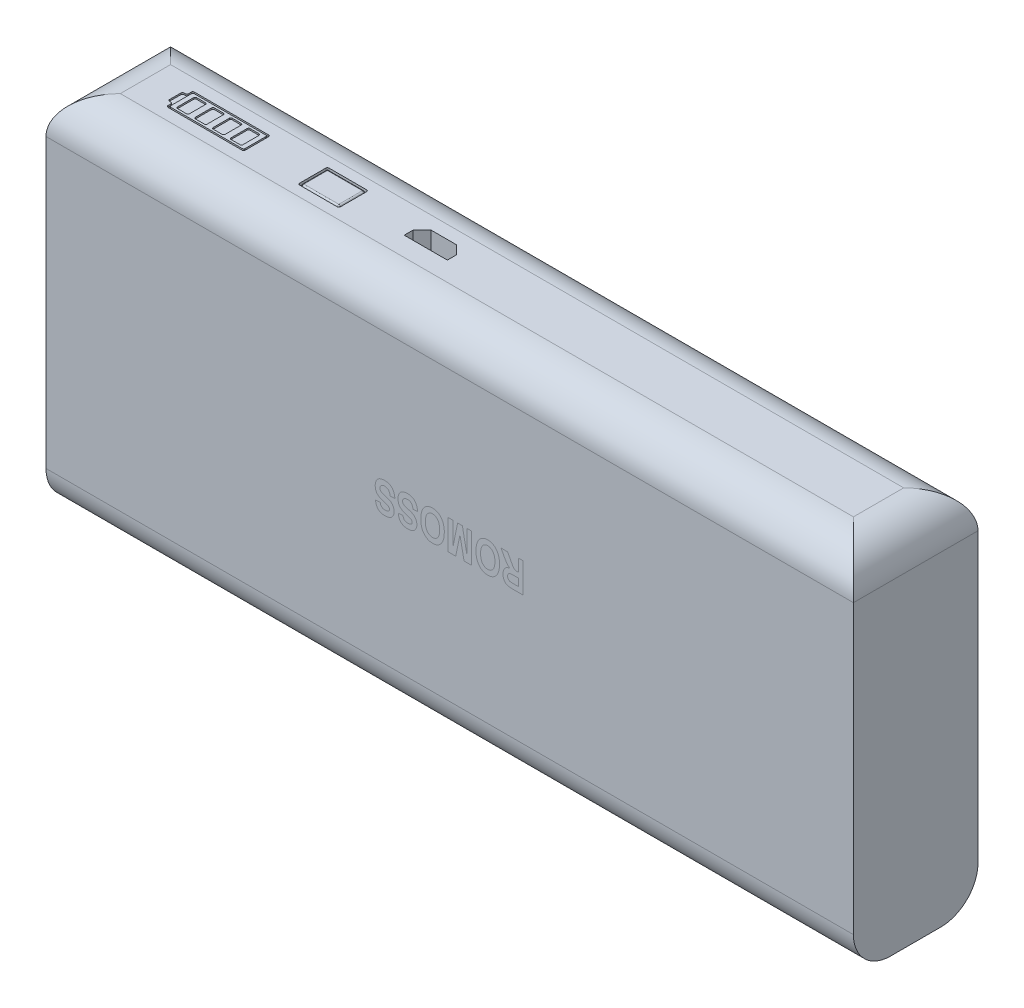
SolidWorks part; units mm, degrees
ref_plane "Front Plane" through (0, 0, 0) normal (0, 0, 1) x (1, 0, 0)
ref_plane "Top Plane" through (0, 0, 0) normal (0, 1, 0) x (1, 0, 0)
ref_plane "Right Plane" through (0, 0, 0) normal (1, 0, 0) x (0, 0, -1)
sketch "Sketch1" plane through (0, 0, 0) normal (0, 1, 0) x (1, 0, 0)
  line L1 (-68.9864, 10.6426) -> (68.9864, 10.6426)
  line L2 (-68.9864, 10.6426) -> (-68.9864, -10.6426)
  line L3 (-68.9864, -10.6426) -> (68.9864, -10.6426)
  line L4 (68.9864, 10.6426) -> (68.9864, -10.6426)
  line L5 (-68.9864, 10.6426) -> (68.9864, -10.6426) construction
  line L6 (-68.9864, -10.6426) -> (68.9864, 10.6426) construction
  point P0 (0, 0)
  dimension "D1" = 137.9728
  dimension "D2" = 21.2852
extrude "Boss-Extrude1" add sketch "Sketch1" along normal blind 61.8236
fillet "Fillet10" radius 6.35 4 edges at (-68.9864, 61.8236, 0) (0, 61.8236, 10.6426) (0, 61.8236, -10.6426) (68.9864, 61.8236, 0)
fillet "Fillet11" radius 6.35 2 edges at (0, 0, 10.6426) (0, 0, -10.6426)
sketch "Sketch3" plane through (0, 0, 10.6426) normal (0, 0, 1) x (1, 0, 0)
  line L0 (-68.9864, 33.4518) -> (68.9864, 33.4518) construction
  line L4 (-62.6364, 61.8236) -> (62.6364, 61.8236) construction
  line L5 (-68.9864, 55.4736) -> (-68.9864, 6.35) construction
  line L6 (68.9864, 55.4736) -> (68.9864, 6.35) construction
  line L7 (-68.9864, 6.35) -> (68.9864, 6.35) construction
  text T0 "ROMOSS\r\n" font "Arial Narrow" height 5.08
  dimension "D1" = 28.3718
sketch "Sketch5" plane through (0, 61.8236, 0) normal (0, 1, 0) x (1, 0, 0)
  line L0 (-56.7944, 2.2606) -> (-56.7944, 1.2446)
  line L1 (-56.5404, 2.0066) -> (-43.8404, 2.0066)
  line L2 (-56.5404, 2.0066) -> (-56.5404, -2.0066)
  line L3 (-56.5404, -2.0066) -> (-43.8404, -2.0066)
  line L4 (-43.8404, 2.0066) -> (-43.8404, -2.0066)
  line L5 (-56.7944, -2.2606) -> (-43.5864, -2.2606)
  line L6 (-43.5864, 2.2606) -> (-43.5864, -2.2606)
  line L7 (-56.7944, 2.2606) -> (-43.5864, 2.2606)
  line L8 (-56.7944, 1.2446) -> (-57.5564, 1.2446)
  line L9 (-57.5564, 1.2446) -> (-57.5564, -1.2446)
  line L10 (-57.5564, -1.2446) -> (-56.7944, -1.2446)
  line L11 (-56.7944, -1.2446) -> (-56.7944, -2.2606)
  line L12 (-56.7944, 2.2606) -> (-56.7944, -2.2606) construction
  line L13 (-62.6364, 4.2926) -> (-62.6364, -4.2926) construction
  line L14 (-62.6364, -4.2926) -> (62.6364, -4.2926) construction
  line L17 (62.6364, 4.2926) -> (-62.6364, 4.2926) construction
  dimension "D2" = 2.032
  dimension "D3" = 12.7
  dimension "D4" = 1.016
  dimension "D5" = 1.016
  dimension "D6" = 1.016
  dimension "D7" = 5.08
  dimension "D8" = 2.032
  dimension "D1" = 0.254
extrude "Cut-Extrude1" cut sketch "Sketch5" against normal blind 0.254
fillet "Fillet12" radius 0.254 12 edges at (-43.5864, 61.6966, -2.2606) (-43.5864, 61.6966, 2.2606) (-43.8404, 61.6966, -2.0066) (-43.8404, 61.6966, 2.0066) (-56.5404, 61.6966, -2.0066) (-56.5404, 61.6966, 2.0066) (-56.7944, 61.6966, 2.2606) (-56.7944, 61.6966, 1.2446) (-56.7944, 61.6966, -1.2446) (-56.7944, 61.6966, -2.2606) (-57.5564, 61.6966, -1.2446) (-57.5564, 61.6966, 1.2446)
sketch "Sketch6" plane through (0, 61.8236, 0) normal (0, 1, 0) x (1, 0, 0)
  line L0 (-44.0944, 2.0066) -> (-56.2864, 2.0066) construction
  line L1 (-55.7784, 1.6256) -> (-53.7464, 1.6256)
  line L2 (-55.7784, 1.6256) -> (-55.7784, -1.6256)
  line L3 (-55.7784, -1.6256) -> (-53.7464, -1.6256)
  line L4 (-53.7464, 1.6256) -> (-53.7464, -1.6256)
  line L5 (-56.2864, -2.0066) -> (-44.0944, -2.0066) construction
  line L6 (-56.5404, 1.7526) -> (-56.5404, -1.7526) construction
  point P6 (-54.7624, -1.6256)
  dimension "D1" = 2.032
  dimension "D2" = 0.381
  dimension "D3" = 0.381
  dimension "D4" = 0.762
extrude "Cut-Extrude2" cut sketch "Sketch6" against normal blind 0.254
fillet "Fillet13" radius 0.254 4 edges at (-53.7464, 61.6966, 1.6256) (-55.7784, 61.6966, 1.6256) (-53.7464, 61.6966, -1.6256) (-55.7784, 61.6966, -1.6256)
pattern_linear "LPattern1" count 4 spacing 3.048 along (1, 0, 0) of "Fillet13", "Cut-Extrude2"
sketch "Sketch7" plane through (0, 61.8236, 0) normal (0, 1, 0) x (1, 0, 0)
  line L1 (-34.0614, 2.5146) -> (-27.0764, 2.5146)
  line L2 (-34.0614, 2.5146) -> (-34.0614, -2.5146)
  line L3 (-34.0614, -2.5146) -> (-27.0764, -2.5146)
  line L4 (-27.0764, 2.5146) -> (-27.0764, -2.5146)
  line L6 (-43.5864, -2.0066) -> (-43.5864, 2.0066) construction
  line L9 (-62.6364, -4.2926) -> (62.6364, -4.2926) construction
  line L10 (62.6364, 4.2926) -> (-62.6364, 4.2926) construction
  dimension "D1" = 6.985
  dimension "D3" = 9.525
  dimension "D4" = 1.778
  dimension "D5" = 1.778
extrude "Cut-Extrude3" cut sketch "Sketch7" against normal blind 0.508
sketch "Sketch8" plane through (0, 61.3156, 0) normal (0, 1, 0) x (1, 0, 0)
  line L0 (-34.0614, -2.5146) -> (-27.0764, -2.5146) construction
  line L1 (-33.8074, 2.2606) -> (-27.3304, 2.2606)
  line L2 (-33.8074, 2.2606) -> (-33.8074, -2.2606)
  line L3 (-33.8074, -2.2606) -> (-27.3304, -2.2606)
  line L4 (-27.3304, 2.2606) -> (-27.3304, -2.2606)
  line L5 (-27.0764, 2.5146) -> (-34.0614, 2.5146) construction
  line L6 (-34.0614, 2.5146) -> (-34.0614, -2.5146) construction
  line L7 (-27.0764, -2.5146) -> (-27.0764, 2.5146) construction
  dimension "D1" = 0.254
  dimension "D2" = 0.254
  dimension "D3" = 0.254
  dimension "D4" = 0.254
extrude "Boss-Extrude2" add sketch "Sketch8" along normal blind 0.508
fillet "Fillet15" radius 0.254 4 edges at (-27.0764, 61.5696, 2.5146) (-27.0764, 61.5696, -2.5146) (-34.0614, 61.5696, -2.5146) (-34.0614, 61.5696, 2.5146)
fillet "Fillet16" radius 0.254 8 edges at (-30.5689, 61.8236, -2.2606) (-27.3304, 61.8236, 0) (-30.5689, 61.8236, 2.2606) (-33.8074, 61.8236, 0) (-33.8074, 61.5696, -2.2606) (-27.3304, 61.5696, -2.2606) (-27.3304, 61.5696, 2.2606) (-33.8074, 61.5696, 2.2606)
sketch "Sketch9" plane through (0, 61.8236, 0) normal (0, 1, 0) x (1, 0, 0)
  line L0 (-17.4244, -0.9906) -> (-10.0584, -0.9906)
  line L1 (-10.0584, -0.9906) -> (-10.0584, 0.5334)
  line L2 (-10.0584, 0.5334) -> (-11.5824, 2.0574)
  line L3 (-11.5824, 2.0574) -> (-15.9004, 2.0574)
  line L4 (-15.9004, 2.0574) -> (-17.4244, 0.5334)
  line L5 (-17.4244, 0.5334) -> (-17.4244, -0.9906)
  line L6 (-62.6364, -4.2926) -> (62.6364, -4.2926) construction
  line L7 (-27.0764, -2.2606) -> (-27.0764, 2.2606) construction
  point P2 (-13.7414, -0.9906)
  point P7 (-13.7414, 2.0574)
  dimension "D1" = 7.366
  dimension "D2" = 3.048
  dimension "D3" = 1.524
  dimension "D4" = 135
  dimension "D5" = 3.302
  dimension "D6" = 9.652
extrude "Cut-Extrude4" cut sketch "Sketch9" against normal blind 6.35
sketch "Sketch10" plane through (-68.9864, 0, 0) normal (-1, 0, 0) x (0, 0, 1)
  line L0 (-10.6426, 55.4736) -> (-10.6426, 6.35) construction
  line L1 (-7.5946, 55.4736) -> (-2.5146, 55.4736)
  line L2 (-7.5946, 55.4736) -> (-7.5946, 42.7736)
  line L3 (-7.5946, 42.7736) -> (-2.5146, 42.7736)
  line L4 (-2.5146, 55.4736) -> (-2.5146, 42.7736)
  line L5 (10.6426, 55.4736) -> (-10.6426, 55.4736) construction
  line L6 (10.6426, 55.4736) -> (10.6426, 6.35) construction
  line L7 (0.9906, 55.4736) -> (6.0706, 55.4736)
  line L8 (0.9906, 55.4736) -> (0.9906, 42.7736)
  line L9 (0.9906, 42.7736) -> (6.0706, 42.7736)
  line L10 (6.0706, 55.4736) -> (6.0706, 42.7736)
  dimension "D1" = 12.7
  dimension "D2" = 5.08
  dimension "D3" = 3.048
  dimension "D4" = 4.572
extrude "Cut-Extrude5" cut sketch "Sketch10" against normal blind 15.24
sketch "Sketch11" plane through (-53.7464, 0, 0) normal (-1, 0, 0) x (0, 0, 1)
  line L0 (-7.5946, 42.7736) -> (-2.5146, 42.7736) construction
  line L1 (-6.0706, 54.8386) -> (-4.8006, 54.8386)
  line L2 (-6.0706, 54.8386) -> (-6.0706, 43.4086)
  line L3 (-6.0706, 43.4086) -> (-4.8006, 43.4086)
  line L4 (-4.8006, 54.8386) -> (-4.8006, 43.4086)
  line L5 (-6.0706, 54.8386) -> (-4.8006, 43.4086) construction
  line L6 (-6.0706, 43.4086) -> (-4.8006, 54.8386) construction
  line L7 (-7.5946, 55.4736) -> (-7.5946, 42.7736) construction
  line L8 (0.9906, 55.4736) -> (0.9906, 42.7736) construction
  line L9 (2.5146, 54.8386) -> (3.7846, 54.8386)
  line L10 (2.5146, 54.8386) -> (2.5146, 43.4086)
  line L11 (2.5146, 43.4086) -> (3.7846, 43.4086)
  line L12 (3.7846, 54.8386) -> (3.7846, 43.4086)
  line L13 (2.5146, 54.8386) -> (3.7846, 43.4086) construction
  line L14 (2.5146, 43.4086) -> (3.7846, 54.8386) construction
  point P0 (-5.4356, 49.1236)
  point P9 (3.1496, 49.1236)
  dimension "D1" = 6.35
  dimension "D2" = 1.524
  dimension "D3" = 11.43
  dimension "D4" = 1.27
  dimension "D5" = 1.524
extrude "Boss-Extrude3" add sketch "Sketch11" along normal blind 11.43
chamfer "Chamfer2" distance 0.508 angle 30 8 edges at (-65.1764, 43.4086, -5.4356) (-65.1764, 49.1236, -6.0706) (-65.1764, 54.8386, -5.4356) (-65.1764, 49.1236, -4.8006) (-65.1764, 43.4086, 3.1496) (-65.1764, 49.1236, 2.5146) (-65.1764, 54.8386, 3.1496) (-65.1764, 49.1236, 3.7846) first distance on face at (-59.4614, 43.4086, -5.4356) first distance on face at (-59.4614, 49.1236, -6.0706) first distance on face at (-59.4614, 54.8386, -5.4356) first distance on face at (-59.4614, 49.1236, -4.8006) first distance on face at (-59.4614, 43.4086, 3.1496) first distance on face at (-59.4614, 49.1236, 2.5146) first distance on face at (-59.4614, 54.8386, 3.1496) first distance on face at (-59.4614, 49.1236, 3.7846)
sketch "Sketch12" plane through (-68.9864, 0, 0) normal (-1, 0, 0) x (0, 0, 1)
  line L0 (3.5306, 39.4716) -> (3.5306, 37.9476) construction
  line L1 (4.8006, 39.4716) -> (4.8006, 37.9476)
  line L2 (2.2606, 39.4716) -> (2.2606, 37.9476)
  line L3 (0.9906, 42.7736) -> (6.0706, 42.7736) construction
  line L4 (-7.5946, 42.7736) -> (-2.5146, 42.7736) construction
  circle A0 centre (-5.0546, 38.7096) radius 1.27
  arc A1 (4.8006, 39.4716) -> (2.2606, 39.4716) centre (3.5306, 39.4716) ccw
  arc A2 (2.2606, 37.9476) -> (4.8006, 37.9476) centre (3.5306, 37.9476) ccw
  point P4 (3.5306, 38.7096)
  point P11 (3.5306, 42.7736)
  point P14 (-5.0546, 42.7736)
  point P15 (3.5306, 40.7416)
  point P16 (3.5306, 36.6776)
  dimension "D1" = 2.54
  dimension "D2" = 4.064
  dimension "D3" = 4.064
extrude "Cut-Extrude6" cut sketch "Sketch12" against normal blind 0.254
wrap "Wrap1" sketch "Sketch3" wrap type scribe source sketch "Sketch3" face at (0, 30.9118, 10.6426)
